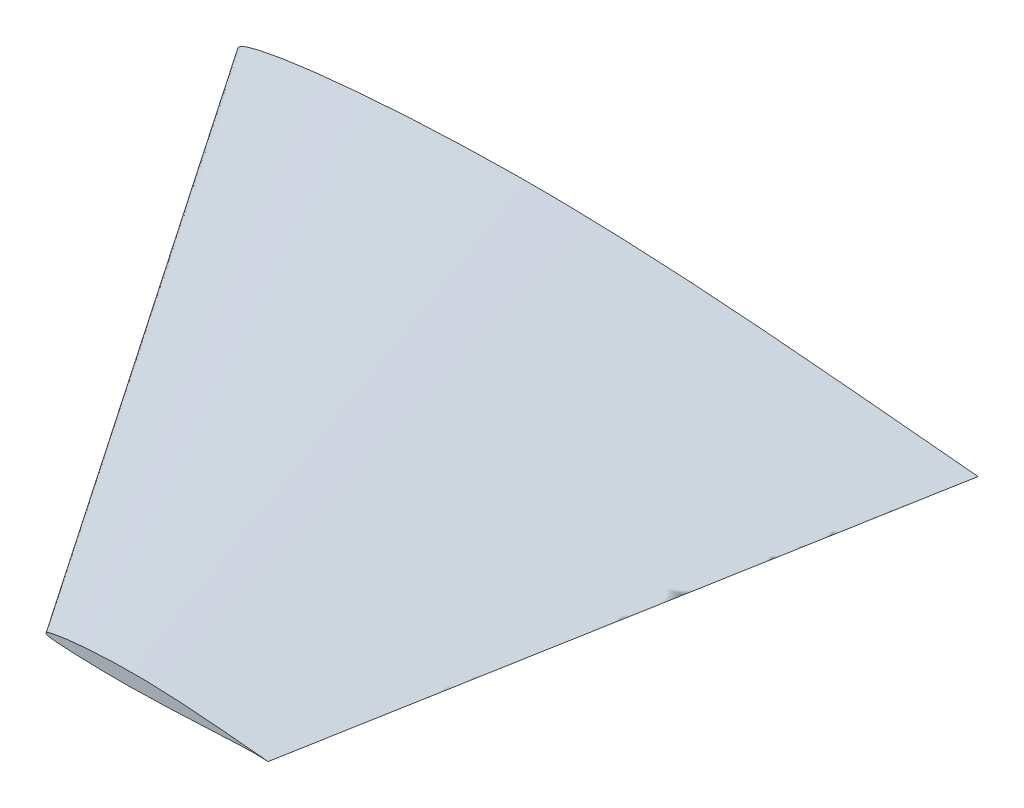
SolidWorks part; units mm, degrees
ref_plane "Front Plane" through (0, 0, 0) normal (0, 0, 1) x (1, 0, 0)
ref_plane "Top Plane" through (0, 0, 0) normal (0, 1, 0) x (1, 0, 0)
ref_plane "Right Plane" through (0, 0, 0) normal (1, 0, 0) x (0, 0, -1)
curve "Curve1"
  spline degree 3 poles (7512.399, 21.2388, 0) (8203.2595, -15.8322, 0) (7513.3519, 42.1095, 0) (7193.4422, 73.6677, 0) (6774.3282, 112.9533, 0) (6381.5746, 149.054, 0) (5981.5484, 184.4784, 0) (5583.1806, 216.6714, 0) (5184.1684, 246.1918, 0) (4785.1429, 271.9717, 0) (4385.9337, 293.3752, 0) (3986.629, 310.1867, 0) (3587.2208, 321.0495, 0) (3187.727, 325.8561, 0) (2788.2189, 320.6453, 0) (2388.7425, 310.365, 0) (1989.2714, 293.5394, 0) (1589.8955, 269.6706, 0) (1190.5368, 238.4305, 0) (858.0326, 204.0929, 0) (592.2576, 169.4022, 0) (392.7788, 138.4756, 0) (226.5583, 105.0644, 0) (114.5266, 76.5641, 0) (61.8453, 55.7367, 0) (27.0243, 39.6534, 0) (-21.8391, -1.9311, 0) (33.3183, -32.9811, 0) (69.4087, -43.6826, 0) (123.6037, -56.5529, 0) (236.6732, -71.2511, 0) (403.6595, -87.6019, 0) (603.2165, -101.4161, 0) (868.9173, -116.5412, 0) (1200.8474, -130.2234, 0) (1599.0388, -142.1668, 0) (1997.0767, -150.2218, 0) (2395.0045, -154.8728, 0) (2792.9004, -155.9632, 0) (3190.7985, -154.6067, 0) (3588.6964, -146.0223, 0) (3986.6382, -133.8676, 0) (4384.6438, -118.3503, 0) (4782.7662, -100.7211, 0) (5180.9825, -81.5014, 0) (5579.4516, -61.1987, 0) (5977.5847, -41.0889, 0) (6377.7846, -21.745, 0) (6771.0798, -3.9492, 0) (7191.075, 6.9211, 0) (7512.399, 21.2388, 0) (8203.2595, -15.8322, 0) (7513.3519, 42.1095, 0) knots -0.074766 -0.049849 -0.024927 0 0.024956 0.049905 0.07487 0.099834 0.124805 0.149776 0.174738 0.199694 0.224645 0.249586 0.27452 0.299451 0.324382 0.34932 0.374267 0.399237 0.424225 0.449262 0.461814 0.474399 0.487067 0.493487 0.496129 0.497491 0.501025 0.504502 0.505834 0.508423 0.514755 0.527287 0.539769 0.552224 0.577107 0.601969 0.626809 0.651646 0.676476 0.701307 0.726142 0.750988 0.775847 0.800716 0.8256 0.850496 0.875398 0.900311 0.925234 0.950151 0.975073 1 1.024956 1.049905 1.07487 periodic
sketch "Sketch2" plane through (0, 0, 0) normal (0, 0, 1) x (1, 0, 0)
  spline S0 degree 3 poles (7512.399, 21.2388) (8203.2595, -15.8322) (7513.3519, 42.1095) (7193.4422, 73.6677) (6774.3282, 112.9533) (6381.5746, 149.054) (5981.5484, 184.4784) (5583.1806, 216.6714) (5184.1684, 246.1918) (4785.1429, 271.9717) (4385.9337, 293.3752) (3986.629, 310.1867) (3587.2208, 321.0495) (3187.727, 325.8561) (2788.2189, 320.6453) (2388.7425, 310.365) (1989.2714, 293.5394) (1589.8955, 269.6706) (1190.5368, 238.4305) (858.0326, 204.0929) (592.2576, 169.4022) (392.7788, 138.4756) (226.5583, 105.0644) (114.5266, 76.5641) (61.8453, 55.7367) (27.0243, 39.6534) (-21.8391, -1.9311) (33.3183, -32.9811) (69.4087, -43.6826) (123.6037, -56.5529) (236.6732, -71.2511) (403.6595, -87.6019) (603.2165, -101.4161) (868.9173, -116.5412) (1200.8474, -130.2234) (1599.0388, -142.1668) (1997.0767, -150.2218) (2395.0045, -154.8728) (2792.9004, -155.9632) (3190.7985, -154.6067) (3588.6964, -146.0223) (3986.6382, -133.8676) (4384.6438, -118.3503) (4782.7662, -100.7211) (5180.9825, -81.5014) (5579.4516, -61.1987) (5977.5847, -41.0889) (6377.7846, -21.745) (6771.0798, -3.9492) (7191.075, 6.9211) (7512.399, 21.2388) (8203.2595, -15.8322) (7513.3519, 42.1095) knots -0.074766 -0.049849 -0.024927 0 0.024956 0.049905 0.07487 0.099834 0.124805 0.149776 0.174738 0.199694 0.224645 0.249586 0.27452 0.299451 0.324382 0.34932 0.374267 0.399237 0.424225 0.449262 0.461814 0.474399 0.487067 0.493487 0.496129 0.497491 0.501025 0.504502 0.505834 0.508423 0.514755 0.527287 0.539769 0.552224 0.577107 0.601969 0.626809 0.651646 0.676476 0.701307 0.726142 0.750988 0.775847 0.800716 0.8256 0.850496 0.875398 0.900311 0.925234 0.950151 0.975073 1 1.024956 1.049905 1.07487 only from (7973.1108, 0) to (7973.1108, 0) construction
  spline S1 degree 3 poles (7512.399, 21.2388) (8203.2595, -15.8322) (7513.3519, 42.1095) (7193.4422, 73.6677) (6774.3282, 112.9533) (6381.5746, 149.054) (5981.5484, 184.4784) (5583.1806, 216.6714) (5184.1684, 246.1918) (4785.1429, 271.9717) (4385.9337, 293.3752) (3986.629, 310.1867) (3587.2208, 321.0495) (3187.727, 325.8561) (2788.2189, 320.6453) (2388.7425, 310.365) (1989.2714, 293.5394) (1589.8955, 269.6706) (1190.5368, 238.4305) (858.0326, 204.0929) (592.2576, 169.4022) (392.7788, 138.4756) (226.5583, 105.0644) (114.5266, 76.5641) (61.8453, 55.7367) (27.0243, 39.6534) (-21.8391, -1.9311) (33.3183, -32.9811) (69.4087, -43.6826) (123.6037, -56.5529) (236.6732, -71.2511) (403.6595, -87.6019) (603.2165, -101.4161) (868.9173, -116.5412) (1200.8474, -130.2234) (1599.0388, -142.1668) (1997.0767, -150.2218) (2395.0045, -154.8728) (2792.9004, -155.9632) (3190.7985, -154.6067) (3588.6964, -146.0223) (3986.6382, -133.8676) (4384.6438, -118.3503) (4782.7662, -100.7211) (5180.9825, -81.5014) (5579.4516, -61.1987) (5977.5847, -41.0889) (6377.7846, -21.745) (6771.0798, -3.9492) (7191.075, 6.9211) (7512.399, 21.2388) (8203.2595, -15.8322) (7513.3519, 42.1095) knots -0.074766 -0.049849 -0.024927 0 0.024956 0.049905 0.07487 0.099834 0.124805 0.149776 0.174738 0.199694 0.224645 0.249586 0.27452 0.299451 0.324382 0.34932 0.374267 0.399237 0.424225 0.449262 0.461814 0.474399 0.487067 0.493487 0.496129 0.497491 0.501025 0.504502 0.505834 0.508423 0.514755 0.527287 0.539769 0.552224 0.577107 0.601969 0.626809 0.651646 0.676476 0.701307 0.726142 0.750988 0.775847 0.800716 0.8256 0.850496 0.875398 0.900311 0.925234 0.950151 0.975073 1 1.024956 1.049905 1.07487 only from (7973.1108, 0) to (7973.1108, 0)
ref_plane "Plane1" through (0, 0, 6480.4442) normal (0, 0, 1) x (1, 0, 0)
curve "Curve2"
  spline degree 3 poles (6670.6549, 6.372, 6480.4442) (6877.925, -4.7499, 6480.4442) (6670.9408, 12.6336, 6480.4442) (6574.9624, 22.1016, 6480.4442) (6449.221, 33.8879, 6480.4442) (6331.3881, 44.7188, 6480.4442) (6211.3734, 55.3467, 6480.4442) (6091.8562, 65.0052, 6480.4442) (5972.1457, 73.8618, 6480.4442) (5852.4312, 81.5962, 6480.4442) (5732.6616, 88.0176, 6480.4442) (5612.8633, 93.0613, 6480.4442) (5493.0339, 96.3204, 6480.4442) (5373.1789, 97.7624, 6480.4442) (5253.3196, 96.1991, 6480.4442) (5133.4699, 93.1148, 6480.4442) (5013.6216, 88.0669, 6480.4442) (4893.802, 80.9058, 6480.4442) (4773.9875, 71.5333, 6480.4442) (4674.2305, 61.2314, 6480.4442) (4594.4935, 50.8236, 6480.4442) (4534.6464, 41.545, 6480.4442) (4484.7774, 31.5211, 6480.4442) (4451.1659, 22.9705, 6480.4442) (4435.3606, 16.722, 6480.4442) (4424.9138, 11.8967, 6480.4442) (4410.2539, -0.5794, 6480.4442) (4426.8021, -9.8949, 6480.4442) (4437.6298, -13.1055, 6480.4442) (4453.8893, -16.9668, 6480.4442) (4487.812, -21.3766, 6480.4442) (4537.9108, -26.2821, 6480.4442) (4597.7813, -30.4266, 6480.4442) (4677.4962, -34.9644, 6480.4442) (4777.0809, -39.0693, 6480.4442) (4896.5452, -42.6525, 6480.4442) (5015.9634, -45.0691, 6480.4442) (5135.3486, -46.4645, 6480.4442) (5254.7242, -46.7916, 6480.4442) (5374.1004, -46.3847, 6480.4442) (5493.4767, -43.8092, 6480.4442) (5612.866, -40.1626, 6480.4442) (5732.2746, -35.5071, 6480.4442) (5851.7182, -30.2181, 6480.4442) (5971.1899, -24.4518, 6480.4442) (6090.7375, -18.3607, 6480.4442) (6210.1843, -12.3274, 6480.4442) (6330.2511, -6.5239, 6480.4442) (6448.2464, -1.1848, 6480.4442) (6574.2522, 2.0764, 6480.4442) (6670.6549, 6.372, 6480.4442) (6877.925, -4.7499, 6480.4442) (6670.9408, 12.6336, 6480.4442) knots -0.074766 -0.049849 -0.024927 0 0.024956 0.049905 0.07487 0.099834 0.124805 0.149776 0.174738 0.199694 0.224645 0.249586 0.27452 0.299451 0.324382 0.34932 0.374267 0.399237 0.424225 0.449262 0.461814 0.474399 0.487067 0.493487 0.496129 0.497491 0.501025 0.504502 0.505834 0.508423 0.514755 0.527287 0.539769 0.552224 0.577107 0.601969 0.626809 0.651646 0.676476 0.701307 0.726142 0.750988 0.775847 0.800716 0.8256 0.850496 0.875398 0.900312 0.925234 0.950151 0.975073 1 1.024956 1.049905 1.07487 periodic
sketch "Sketch3" plane through (0, 0, 6480.4442) normal (0, 0, 1) x (1, 0, 0)
  spline S0 degree 3 poles (6670.6549, 6.372) (6877.925, -4.7499) (6670.9408, 12.6336) (6574.9624, 22.1016) (6449.221, 33.8879) (6331.3881, 44.7188) (6211.3734, 55.3467) (6091.8562, 65.0052) (5972.1457, 73.8618) (5852.4312, 81.5962) (5732.6616, 88.0176) (5612.8633, 93.0613) (5493.0339, 96.3204) (5373.1789, 97.7624) (5253.3196, 96.1991) (5133.4699, 93.1148) (5013.6216, 88.0669) (4893.802, 80.9058) (4773.9875, 71.5333) (4674.2305, 61.2314) (4594.4935, 50.8236) (4534.6464, 41.545) (4484.7774, 31.5211) (4451.1659, 22.9705) (4435.3606, 16.722) (4424.9138, 11.8967) (4410.2539, -0.5794) (4426.8021, -9.8949) (4437.6298, -13.1055) (4453.8893, -16.9668) (4487.812, -21.3766) (4537.9108, -26.2821) (4597.7813, -30.4266) (4677.4962, -34.9644) (4777.0809, -39.0693) (4896.5452, -42.6525) (5015.9634, -45.0691) (5135.3486, -46.4645) (5254.7242, -46.7916) (5374.1004, -46.3847) (5493.4767, -43.8092) (5612.866, -40.1626) (5732.2746, -35.5071) (5851.7182, -30.2181) (5971.1899, -24.4518) (6090.7375, -18.3607) (6210.1843, -12.3274) (6330.2511, -6.5239) (6448.2464, -1.1848) (6574.2522, 2.0764) (6670.6549, 6.372) (6877.925, -4.7499) (6670.9408, 12.6336) knots -0.074766 -0.049849 -0.024927 0 0.024956 0.049905 0.07487 0.099834 0.124805 0.149776 0.174738 0.199694 0.224645 0.249586 0.27452 0.299451 0.324382 0.34932 0.374267 0.399237 0.424225 0.449262 0.461814 0.474399 0.487067 0.493487 0.496129 0.497491 0.501025 0.504502 0.505834 0.508423 0.514755 0.527287 0.539769 0.552224 0.577107 0.601969 0.626809 0.651646 0.676476 0.701307 0.726142 0.750988 0.775847 0.800716 0.8256 0.850496 0.875398 0.900312 0.925234 0.950151 0.975073 1 1.024956 1.049905 1.07487 only from (6808.8764, 0) to (6808.8764, 0) construction
  spline S1 degree 3 poles (6670.6549, 6.372) (6877.925, -4.7499) (6670.9408, 12.6336) (6574.9624, 22.1016) (6449.221, 33.8879) (6331.3881, 44.7188) (6211.3734, 55.3467) (6091.8562, 65.0052) (5972.1457, 73.8618) (5852.4312, 81.5962) (5732.6616, 88.0176) (5612.8633, 93.0613) (5493.0339, 96.3204) (5373.1789, 97.7624) (5253.3196, 96.1991) (5133.4699, 93.1148) (5013.6216, 88.0669) (4893.802, 80.9058) (4773.9875, 71.5333) (4674.2305, 61.2314) (4594.4935, 50.8236) (4534.6464, 41.545) (4484.7774, 31.5211) (4451.1659, 22.9705) (4435.3606, 16.722) (4424.9138, 11.8967) (4410.2539, -0.5794) (4426.8021, -9.8949) (4437.6298, -13.1055) (4453.8893, -16.9668) (4487.812, -21.3766) (4537.9108, -26.2821) (4597.7813, -30.4266) (4677.4962, -34.9644) (4777.0809, -39.0693) (4896.5452, -42.6525) (5015.9634, -45.0691) (5135.3486, -46.4645) (5254.7242, -46.7916) (5374.1004, -46.3847) (5493.4767, -43.8092) (5612.866, -40.1626) (5732.2746, -35.5071) (5851.7182, -30.2181) (5971.1899, -24.4518) (6090.7375, -18.3607) (6210.1843, -12.3274) (6330.2511, -6.5239) (6448.2464, -1.1848) (6574.2522, 2.0764) (6670.6549, 6.372) (6877.925, -4.7499) (6670.9408, 12.6336) knots -0.074766 -0.049849 -0.024927 0 0.024956 0.049905 0.07487 0.099834 0.124805 0.149776 0.174738 0.199694 0.224645 0.249586 0.27452 0.299451 0.324382 0.34932 0.374267 0.399237 0.424225 0.449262 0.461814 0.474399 0.487067 0.493487 0.496129 0.497491 0.501025 0.504502 0.505834 0.508423 0.514755 0.527287 0.539769 0.552224 0.577107 0.601969 0.626809 0.651646 0.676476 0.701307 0.726142 0.750988 0.775847 0.800716 0.8256 0.850496 0.875398 0.900312 0.925234 0.950151 0.975073 1 1.024956 1.049905 1.07487 only from (6808.8764, 0) to (6808.8764, 0)
loft "Loft1" add profiles "Sketch3", "Sketch2" connector at (4416.8157, 1.0935, 6480.4442) connector at (0.8512, 7.4791, 0)
